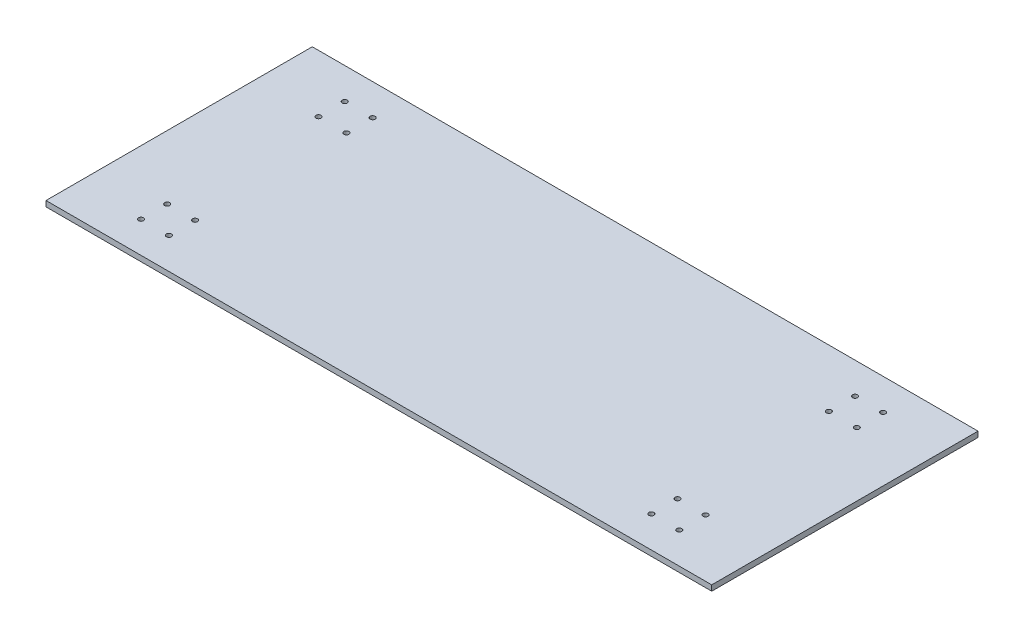
SolidWorks part; units mm, degrees
ref_plane "Front Plane" through (0, 0, 0) normal (0, 0, 1) x (1, 0, 0)
ref_plane "Top Plane" through (0, 0, 0) normal (0, 1, 0) x (1, 0, 0)
ref_plane "Right Plane" through (0, 0, 0) normal (1, 0, 0) x (0, 0, -1)
sketch "Sketch1" plane through (0, 0, 0) normal (0, 1, 0) x (1, 0, 0)
  line L1 (-381, 152.4) -> (381, 152.4)
  line L2 (-381, 152.4) -> (-381, -152.4)
  line L3 (-381, -152.4) -> (381, -152.4)
  line L4 (381, 152.4) -> (381, -152.4)
  line L5 (-381, 152.4) -> (381, -152.4) construction
  line L6 (-381, -152.4) -> (381, 152.4) construction
  point P0 (0, 0)
  dimension "D1" = 304.8
  dimension "D2" = 762
extrude "Boss-Extrude1" add sketch "Sketch1" along normal blind 6.35
ref_plane "Front" through (0, 0, 152.4) normal (0, 0, 1) x (1, 0, 0)
hole_wizard "M5 Clearance Hole1" positions "Sketch4" profile "Sketch5" hole size "M5" standard "ANSI Metric" end condition up to next
sketch "Sketch4" plane through (0, 6.35, 0) normal (0, 1, 0) x (1, 0, 0)
  circle A0 centre (276.1, 116.6) radius 2.5 construction
  circle A1 centre (276.1, 86.6) radius 2.5 construction
  circle A2 centre (308.1, 116.6) radius 2.5 construction
  circle A3 centre (308.1, 86.6) radius 2.5 construction
  circle A4 centre (276.1, -86.6) radius 2.5 construction
  circle A5 centre (276.1, -116.6) radius 2.5 construction
  circle A6 centre (308.1, -86.6) radius 2.5 construction
  circle A7 centre (308.1, -116.6) radius 2.5 construction
  circle A8 centre (-308.1, 116.6) radius 2.5 construction
  circle A9 centre (-308.1, 86.6) radius 2.5 construction
  circle A10 centre (-276.1, 116.6) radius 2.5 construction
  circle A11 centre (-276.1, 86.6) radius 2.5 construction
  circle A12 centre (-276.1, -86.6) radius 2.5 construction
  circle A13 centre (-276.1, -116.6) radius 2.5 construction
  circle A14 centre (-308.1, -116.6) radius 2.5 construction
  circle A15 centre (-308.1, -86.6) radius 2.5 construction
  circle A16 centre (276.1, 116.6) radius 2.5 construction
  circle A17 centre (276.1, 86.6) radius 2.5 construction
  circle A18 centre (308.1, 116.6) radius 2.5 construction
  circle A19 centre (308.1, 86.6) radius 2.5 construction
  circle A20 centre (276.1, -86.6) radius 2.5 construction
  circle A21 centre (276.1, -116.6) radius 2.5 construction
  circle A22 centre (308.1, -86.6) radius 2.5 construction
  circle A23 centre (308.1, -116.6) radius 2.5 construction
  circle A24 centre (-308.1, 116.6) radius 2.5 construction
  circle A25 centre (-308.1, 86.6) radius 2.5 construction
  circle A26 centre (-276.1, 116.6) radius 2.5 construction
  circle A27 centre (-276.1, 86.6) radius 2.5 construction
  circle A28 centre (-276.1, -86.6) radius 2.5 construction
  circle A29 centre (-276.1, -116.6) radius 2.5 construction
  circle A30 centre (-308.1, -116.6) radius 2.5 construction
  circle A31 centre (-308.1, -86.6) radius 2.5 construction
  point P1 (276.1, 116.6)
  point P3 (276.1, 86.6)
  point P5 (308.1, 116.6)
  point P7 (308.1, 86.6)
  point P9 (276.1, -86.6)
  point P11 (276.1, -116.6)
  point P13 (308.1, -86.6)
  point P15 (308.1, -116.6)
  point P17 (-308.1, 116.6)
  point P19 (-308.1, 86.6)
  point P21 (-276.1, 116.6)
  point P23 (-276.1, 86.6)
  point P25 (-276.1, -86.6)
  point P27 (-276.1, -116.6)
  point P29 (-308.1, -116.6)
  point P31 (-308.1, -86.6)
sketch "Sketch5" plane through (276.1, 6.35, -116.6) normal (1, 0, 0) x (0, 0, 1)
  line L0 (0, 0) -> (0, 6.35)
  line L1 (0, 6.35) -> (2.9, 6.35)
  line L2 (2.9, 6.35) -> (2.9, 0)
  line L5 (2.9, 0) -> (0, 0)
  line L11 (0, -6.35) -> (0, 107.95) construction
  dimension "Thru Hole Dia." = 5.8
  dimension "Thru Hole Depth" = 6.35
equation "\"height\"= .25in"
equation "\"width\"= 30in"
equation "\"depth\"= 12in"
equation "\"D1@Sketch1\" = \"depth\""
equation "\"D2@Sketch1\"= \"width\""
equation "\"D1@Boss-Extrude1\"= \"height\""
